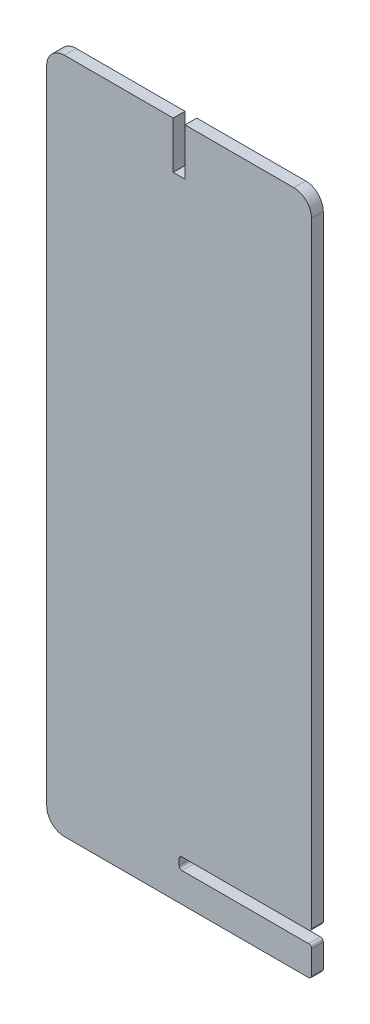
SolidWorks part; units mm, degrees
ref_plane "Alzado" through (0, 0, 0) normal (0, 0, 1) x (1, 0, 0)
ref_plane "Planta" through (0, 0, 0) normal (0, 1, 0) x (1, 0, 0)
ref_plane "Vista lateral" through (0, 0, 0) normal (1, 0, 0) x (0, 0, -1)
sketch "Croquis1" plane through (0, 0, 0) normal (0, 0, 1) x (1, 0, 0)
  line L1 (-22.5, 45) -> (22.5, 45)
  line L2 (-22.5, 45) -> (-22.5, -70)
  line L3 (-22.5, -70) -> (22.5, -70)
  line L4 (22.5, 45) -> (22.5, -70)
  dimension "D1" = 45
  dimension "D2" = 22.5
  dimension "D3" = 115
  dimension "D4" = 45
extrude "Saliente-Extruir1" add sketch "Croquis1" along normal blind 2 contours L2 L3 L4 L1
sketch "Croquis3" plane through (0, 0, 2) normal (0, 0, 1) x (1, 0, 0)
  line L0 (22.5, 45) -> (22.5, -70) construction
  line L1 (22.5, -63) -> (0, -63)
  line L2 (22.5, -63) -> (22.5, -65)
  line L3 (22.5, -65) -> (0, -65)
  line L4 (0, -63) -> (0, -65)
  line L5 (-22.5, -70) -> (22.5, -70) construction
  dimension "D1" = 2
  dimension "D2" = 5
  dimension "D3" = 22.5
extrude "Cortar-Extruir2" cut sketch "Croquis3" against normal up to surface (2 mm away) up to face at (0, -12.5, 0)
fillet "Redondeo1" radius 3 3 edges at (-22.5, -70, 1) (22.5, 45, 1) (-22.5, 45, 1)
sketch "Croquis4" plane through (0, 0, 2) normal (0, 0, 1) x (1, 0, 0)
  line L5 (0, 0) -> (0, 53.685) construction
  line L6 (-19.5, 45) -> (19.5, 45) construction
  line L7 (-1, 45) -> (1, 45)
  line L8 (-1, 45) -> (-1, 37)
  line L9 (-1, 37) -> (1, 37)
  line L10 (1, 45) -> (1, 37)
  dimension "D1" = 1
  dimension "D2" = 1
  dimension "D3" = 8
extrude "Cortar-Extruir3" cut sketch "Croquis4" against normal up to surface (2 mm away) up to face at (2.2617, -26.2162, 0)
fillet "Redondeo2" radius 0.5 5 edges at (0, -63, 1) (0, -65, 1) (22.5, -70, 1) (22.5, -65, 1) (22.5, -63, 1)
